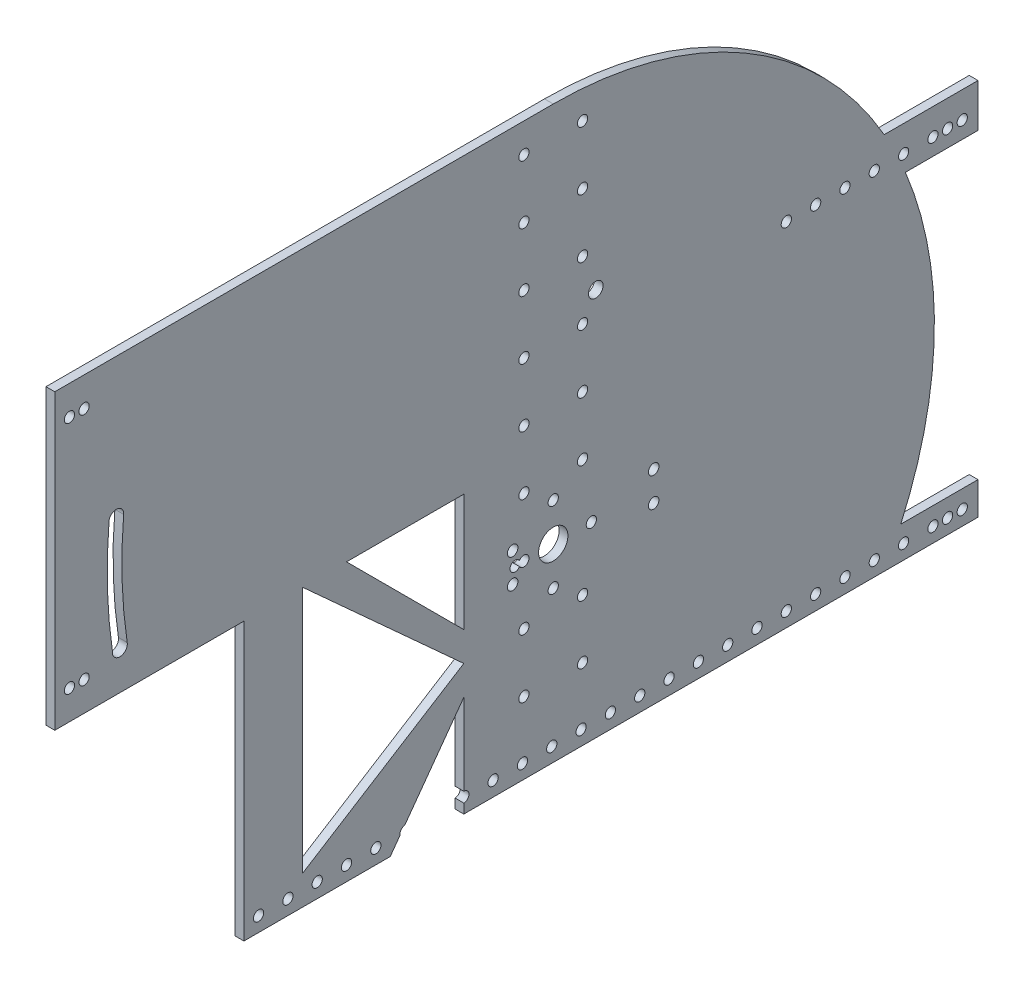
SolidWorks part; units mm, degrees
ref_plane "Front Plane" through (0, 0, 0) normal (0, 0, 1) x (1, 0, 0)
ref_plane "Top Plane" through (0, 0, 0) normal (0, 1, 0) x (1, 0, 0)
ref_plane "Right Plane" through (0, 0, 0) normal (1, 0, 0) x (0, 0, -1)
sketch "Sketch1" plane through (0, 0, 0) normal (1, 0, 0) x (0, 0, -1)
  line L0 (0, 130) -> (-170, 130)
  line L1 (-170, 130) -> (-170, 30)
  line L2 (-170, 30) -> (-126.4911, 30)
  arc A0 (-126.4911, 30) -> (0, 130) centre (0, 0) ccw
  circle A1 centre (0, 0) radius 5
  dimension "D1" = 260
  dimension "D2" = 10
  dimension "D3" = 100
  dimension "D4" = 170
extrude "Boss-Extrude1" add sketch "Sketch1" along normal blind 3
sketch "Sketch2" plane through (3, 0, 0) normal (1, 0, 0) x (0, 0, -1)
  line L0 (-10, 10) -> (-10, -10) construction
  line L1 (-10, -10) -> (30.4, -10) construction
  line L2 (30.4, -10) -> (30.4, 10) construction
  line L3 (30.4, 10) -> (-10, 10) construction
  circle A1 centre (0, 0) radius 5 construction
  circle A2 centre (-13.85, 5) radius 1.8
  circle A3 centre (-13.85, -5) radius 1.8
  circle A4 centre (34.25, 5) radius 1.8
  circle A5 centre (34.25, -5) radius 1.8
  circle A7 centre (0, 13) radius 1.75
  circle A8 centre (13, 0) radius 1.75
  circle A9 centre (0, -13) radius 1.75
  circle A10 centre (-13, 0) radius 1.75
  point P11 (-10, 0)
  point P27 (0, 0)
  dimension "D1" = 10
  dimension "D2" = 10
  dimension "D4" = 3.6
  dimension "D7" = 3.85
  dimension "D8" = 5
  dimension "D10" = 5
  dimension "D12" = 3.85
  dimension "D13" = 10
  dimension "D6" = 3.5
  dimension "D14" = 13
  dimension "D3" = 40.4
  dimension "D5" = 20
  dimension "D9" = 10
  dimension "D11" = 3.85
  dimension "D15" = 4
extrude "ServoHole" cut sketch "Sketch2" against normal through all
sketch "Sketch3" plane through (3, 0, 0) normal (1, 0, 0) x (0, 0, -1)
  line L1 (123.9473, -130) -> (-198.7557, -130)
  line L2 (123.9473, -130) -> (123.9473, -64.5)
  line L3 (123.9473, -64.5) -> (-198.7557, -64.5)
  line L4 (-198.7557, -130) -> (-198.7557, -64.5)
  arc A0 (-126.4911, 30) -> (0, 130) centre (0, 0) ccw construction
  dimension "D1" = 130
  dimension "D2" = 64.5
extrude "Cut-Extrude2" cut sketch "Sketch3" against normal through all
sketch "Sketch4" plane through (3, 0, 0) normal (1, 0, 0) x (0, 0, -1)
  line L1 (-170, 30) -> (-105.5, 30)
  line L2 (-170, 30) -> (-170, -85)
  line L3 (-170, -85) -> (-105.5, -85)
  line L4 (-30.5, 30) -> (-30.5, -10)
  line L6 (-70.5, 30) -> (-30.5, -10)
  line L7 (-85.5, 30) -> (-30.5, -20)
  line L8 (-30.5, -20) -> (-85.5, -54.5)
  line L9 (-30.5, -30) -> (-70.5, -85)
  line L10 (-70.5, 30) -> (-30.5, 30)
  line L11 (-30.5, -30) -> (-30.5, -85)
  line L12 (-70.5, -85) -> (-30.5, -85)
  line L13 (-85.5, 30) -> (-85.5, -54.5)
  line L14 (-105.5, 30) -> (-105.5, -85)
  line L15 (112.8705, -64.5) -> (-112.8705, -64.5) construction
  circle A0 centre (0, 0) radius 5 construction
  dimension "D2" = 40
  dimension "D3" = 45
  dimension "D4" = 10
  dimension "D5" = 10
  dimension "D6" = 15
  dimension "D7" = 20
  dimension "D8" = 40
  dimension "D9" = 20
  dimension "D10" = 10
  dimension "D11" = 115
  dimension "D12" = 30.5
extrude "Cut-Extrude5" cut sketch "Sketch4" against normal through all
sketch "Sketch5" plane through (3, 0, 0) normal (1, 0, 0) x (0, 0, -1)
  line L0 (112.8705, -64.5) -> (-30.5, -64.5) construction
  line L1 (-30.5, -64.5) -> (-30.5, -30) construction
  circle A0 centre (-20.5, -59.5) radius 1.75
  dimension "D1" = 3.5
  dimension "D2" = 5
  dimension "D3" = 10
extrude "Cut-Extrude6" cut sketch "Sketch5" against normal blind 10
pattern_linear "LPattern1" count 14 spacing 10 along (0, 0, -1) of "Cut-Extrude6"
pattern_linear "LPattern2" count 14 spacing 10 along (0, 0, 1) of "Cut-Extrude6"
sketch "Sketch6" plane through (3, 0, 0) normal (1, 0, 0) x (0, 0, -1)
  circle A0 centre (109.5, 55.5) radius 1.75
  circle A1 centre (109.5, -59.5) radius 1.75 construction
  circle A2 centre (99.5, -59.5) radius 1.75 construction
  circle A3 centre (99.5, 55.5) radius 1.75
  circle A4 centre (89.5, 55.5) radius 1.75
  circle A5 centre (79.5, 55.5) radius 1.75
  dimension "D1" = 3.5
  dimension "D2" = 115
  dimension "D3" = 10
  dimension "D5" = 10
  dimension "D4" = 4
extrude "Cut-Extrude7" cut sketch "Sketch6" against normal blind 10
sketch "Sketch7" plane through (3, 0, 0) normal (1, 0, 0) x (0, 0, -1)
  line L0 (112.8705, -64.5) -> (144.8705, -64.5)
  line L1 (144.8705, -64.5) -> (144.8705, -53.383)
  line L2 (144.8705, -53.383) -> (118.5338, -53.383)
  line L3 (112.8705, 64.5) -> (144.8705, 64.5)
  line L4 (144.8705, 64.5) -> (144.8705, 49.7546)
  line L5 (144.8705, 49.7546) -> (120.102, 49.7546)
  arc A0 (112.8705, -64.5) -> (0, 130) centre (0, 0) ccw construction
  arc A1 (112.8705, -64.5) -> (118.5338, -53.383) centre (0, 0) ccw
  arc A2 (120.102, 49.7546) -> (112.8705, 64.5) centre (0, 0) ccw
  circle A3 centre (109.5, -59.5) radius 1.75 construction
  circle A4 centre (109.5, 55.5) radius 1.75 construction
  circle A5 centre (109.5, -59.5) radius 1.75 construction
  circle A6 centre (109.5, 55.5) radius 1.75 construction
  circle A7 centre (119.5, 55.5) radius 1.75
  circle A8 centre (129.5, 55.5) radius 1.75
  circle A9 centre (139.5, 55.5) radius 1.75
  circle A11 centre (119.5, -59.5) radius 1.75
  circle A12 centre (129.5, -59.5) radius 1.75
  circle A13 centre (139.5, -59.5) radius 1.75
  circle A15 centre (149.5, 55.5) radius 1.75 [skipped]
  circle A16 centre (149.5, -59.5) radius 1.75 [skipped]
  circle A17 centre (134.5, -59.5) radius 1.75
  circle A18 centre (134.5, 55.5) radius 1.75
  dimension "D4" = 10
  dimension "D6" = 5
  dimension "D8" = 10
  dimension "D10" = 5
  dimension "D3" = 32
  dimension "D7" = 32
  dimension "D1" = 5
  dimension "D2" = 5
  dimension "D5" = 2
  dimension "D9" = 2
extrude "Boss-Extrude2" add sketch "Sketch7" against normal blind 3
sketch "Sketch8" plane through (0, 0, 0) normal (-1, 0, 0) x (0, 0, 1)
  circle A0 centre (-14.5, 67.89) radius 2.5
  circle A1 centre (-79.5, 55.5) radius 1.75 construction
  arc A2 (146.5155, 82.0337) -> (145.2961, 43.5745) centre (-14.5, 67.89) cw
  arc A3 (151.5342, 82.0337) -> (150.3519, 43.5745) centre (-14.5, 67.89) cw
  arc A4 (145.2961, 43.5745) -> (150.3519, 43.5745) centre (147.824, 43.1898) ccw
  arc A5 (146.5155, 82.0337) -> (151.5342, 82.0337) centre (149.0248, 82.2541) cw
  dimension "D1" = 5
  dimension "D2" = 65
  dimension "D3" = 12.39
  dimension "D4" = 5
extrude "Cut-Extrude8" cut sketch "Sketch8" against normal blind 3
sketch "Sketch9" plane through (0, 0, 0) normal (-1, 0, 0) x (0, 0, 1)
  line L0 (0, 130) -> (170, 130) construction
  line L1 (170, 130) -> (170, 30) construction
  line L2 (170, 30) -> (105.5, 30) construction
  circle A0 centre (160, 40) radius 1.75
  circle A2 centre (160, 120) radius 1.75
  circle A4 centre (165, 40) radius 1.75
  circle A5 centre (165, 120) radius 1.75
  dimension "D1" = 3.5
  dimension "D2" = 10
  dimension "D3" = 10
  dimension "D4" = 10
  dimension "D5" = 10
  dimension "D6" = 2
extrude "Cut-Extrude9" cut sketch "Sketch9" against normal blind 10
sketch "Sketch10" plane through (0, 0, 0) normal (-1, 0, 0) x (0, 0, 1)
  line L0 (-144.8705, -64.5) -> (30.5, -64.5) construction
  line L4 (0, 130) -> (0, -64.5) construction
  line L5 (170, 130) -> (170, 30) construction
  line L6 (0, 130) -> (170, 130) construction
  circle A0 centre (10, 120) radius 1.75
  circle A2 centre (10, 100) radius 1.75
  circle A3 centre (10, 80) radius 1.75
  circle A4 centre (10, 60) radius 1.75
  circle A5 centre (10, 40) radius 1.75
  circle A6 centre (10, 20) radius 1.75
  circle A7 centre (10, 0) radius 1.75
  circle A8 centre (10, -20) radius 1.75
  circle A9 centre (10, -40) radius 1.75
  circle A10 centre (-10, 20) radius 1.75
  circle A11 centre (-10, -20) radius 1.75
  circle A12 centre (-10, -40) radius 1.75
  circle A13 centre (-10, 40) radius 1.75
  circle A14 centre (-10, 60) radius 1.75
  circle A15 centre (-10, 80) radius 1.75
  circle A16 centre (-10, 100) radius 1.75
  circle A17 centre (-10, 120) radius 1.75
  dimension "D2" = 10
  dimension "D3" = 10
  dimension "D4" = 3.5
  dimension "D6" = 20
  dimension "D1" = 170
  dimension "D5" = 9
extrude "Cut-Extrude10" cut sketch "Sketch10" against normal blind 10
